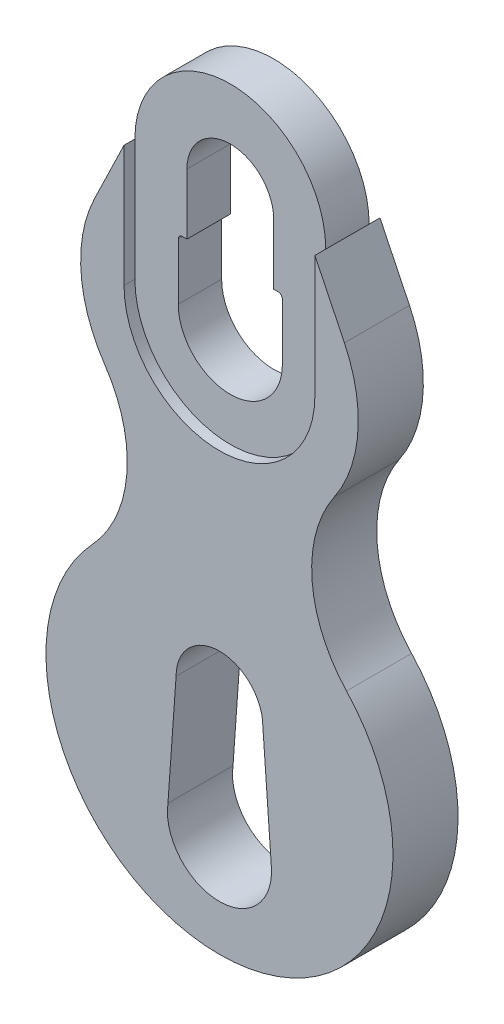
SolidWorks part; units mm, degrees
ref_plane "Front Plane" through (0, 0, 0) normal (0, 0, 1) x (1, 0, 0)
ref_plane "Top Plane" through (0, 0, 0) normal (0, 1, 0) x (1, 0, 0)
ref_plane "Right Plane" through (0, 0, 0) normal (1, 0, 0) x (0, 0, -1)
sketch "Sketch1" plane through (0, 0, 0) normal (0, 0, 1) x (1, 0, 0)
  line L0 (0, 50000) -> (0, 134.5634) construction
  line L1 (50000, 0) -> (-50000, 0) construction
  line L2 (-10, 10.5634) -> (-12, -17.4366)
  line L3 (10, 10.5634) -> (12.0376, -17.5196)
  line L4 (10, 110.5634) -> (10, 96.5634)
  line L5 (22, 110.5634) -> (22, 82.5634)
  line L6 (-22, 110.5634) -> (-22, 82.5634)
  line L11 (0, 82.5634) -> (0, 50.5634) construction
  line L12 (10, 96.5634) -> (11, 96.5634)
  line L13 (12, 95.5634) -> (12, 82.5634)
  line L14 (-10, 96.5634) -> (-11, 96.5634)
  line L15 (-12, 95.5634) -> (-12, 82.5634)
  line L16 (-10, 110.5634) -> (-10, 96.5634)
  line L17 (-22, 110.5634) -> (-28.8044, 96.5028)
  line L18 (22, 110.5634) -> (28.8044, 96.5028)
  line L19 (0, 20.5634) -> (0, -50000) construction
  arc A0 (-29.2877, 27.2439) -> (29.2877, 27.2439) centre (0, 0) ccw
  arc A1 (10, 10.5634) -> (-10, 10.5634) centre (0, 10.5634) ccw
  arc A2 (-11.8782, -15.731) -> (11.9685, -16.5682) centre (0, -17.4366) ccw
  arc A3 (22, 110.5634) -> (-22, 110.5634) centre (0, 110.5634) ccw
  arc A4 (-22, 82.5634) -> (22, 82.5634) centre (0, 82.5634) ccw
  arc A9 (10, 110.5634) -> (-10, 110.5634) centre (0, 110.5634) ccw
  arc A10 (-12, 82.5634) -> (12, 82.5634) centre (0, 82.5634) ccw
  arc A11 (11, 96.5634) -> (12, 95.5634) centre (11, 95.5634) cw
  arc A12 (-11, 96.5634) -> (-12, 95.5634) centre (-11, 95.5634) ccw
  arc A13 (-28.8044, 96.5028) -> (-26.4534, 64.5574) centre (0, 82.5634) ccw
  arc A14 (26.4534, 64.5574) -> (29.2877, 27.2439) centre (51.2535, 47.6768) ccw
  arc A15 (-26.4534, 64.5574) -> (-29.2877, 27.2439) centre (-51.2535, 47.6768) cw
  arc A16 (26.4534, 64.5574) -> (28.8044, 96.5028) centre (0, 82.5634) ccw
  point P17 (0, 110.5634)
  point P29 (-21.3397, 45.4046)
  point P32 (12, 96.5634)
  point P46 (0, 0)
  dimension "D1" = 24
  dimension "D2" = 20
  dimension "D3" = 80
  dimension "D5" = 11.9695
  dimension "D8" = 22
  dimension "D11" = 24
  dimension "D12" = 20
  dimension "D13" = 14
  dimension "D14" = 1
  dimension "D15" = 128
  dimension "D17" = 22
  dimension "D18" = 30
  dimension "D19" = 64
  dimension "D20" = 19.803
  dimension "D21" = 42.8505
  dimension "D22" = 30
  dimension "D23" = 37.1588
  dimension "D4" = 28
  dimension "D6" = 12.0376
  dimension "D7" = 10.5634
  dimension "D9" = 28
  dimension "D10" = 14
  dimension "D16" = 28
  dimension "D24" = 15.6205
extrude "Boss-Extrude3" add sketch "Sketch1" along normal mid plane 10 contours L6 A4 L5 A3 A12 L14 L16 A9 L4 L12 A11 L13 A10 L15 region at (21.1562, 96.5634, 0)
extrude "Boss-Extrude4" add sketch "Sketch1<5>" along normal mid plane 15 contours A14 A16 L18 L5 A4 L6 L17 A13 A15 A0 A2 L2 A1 L3 region at (-0.0008, 21.0047, 0)
sketch "Sketch1<5>" plane through (0, 0, 0) normal (0, 0, 1) x (1, 0, 0) same geometry as "Sketch1"
